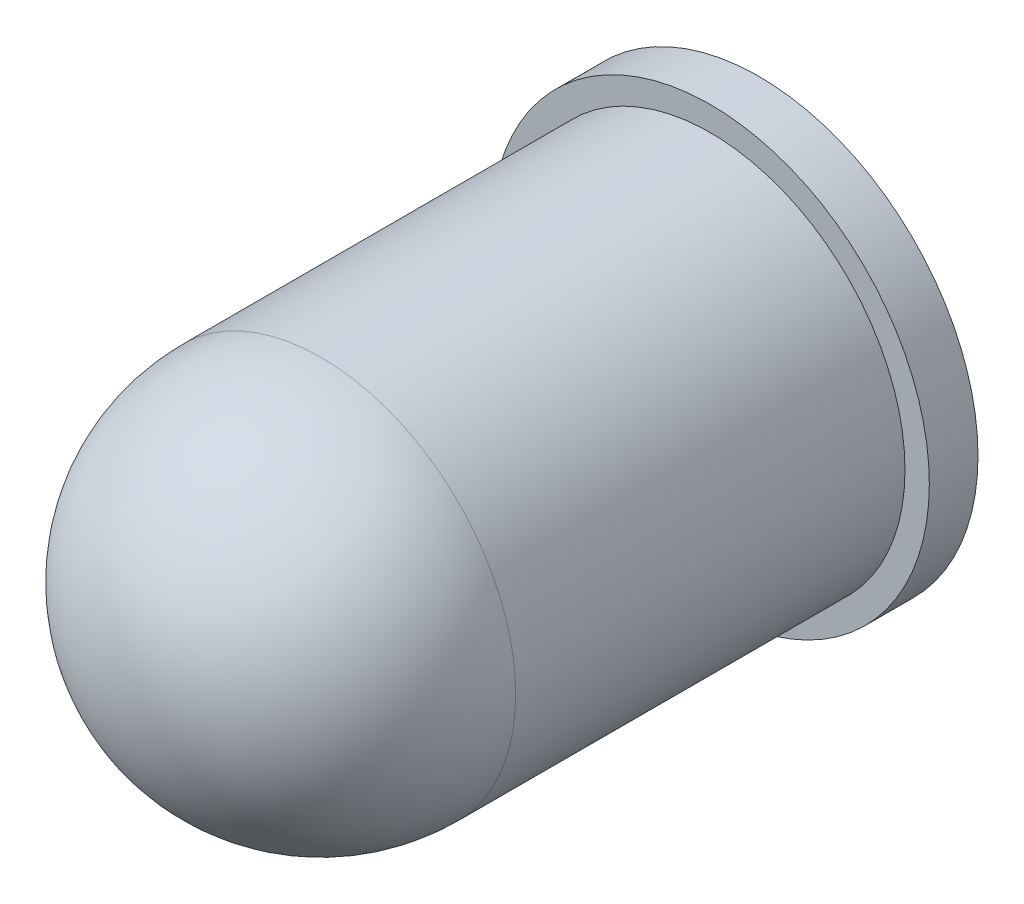
SolidWorks part; units mm, degrees
material "Glass"
ref_plane "Front Plane" through (0, 0, 0) normal (1, 0, 0) x (0, 1, 0)
ref_plane "Top Plane" through (0, 0, 0) normal (0, 0, 1) x (0, 1, 0)
ref_plane "Right Plane" through (0, 0, 0) normal (0, 1, 0) x (-1, 0, 0)
sketch "Sketch1" plane through (0, 0, 0) normal (1, 0, 0) x (0, 1, 0)
  line L0 (0, 10.8055) -> (0, -4.1754) construction
  line L1 (-3.4613, 0) -> (5.0124, 0) construction
  line L3 (0, 1) -> (4.5, 1)
  line L4 (4.5, 1) -> (4.5, 0)
  line L5 (4.5, 0) -> (0, 0)
  line L6 (4, 1) -> (4, 9)
  line L7 (4, 9) -> (0, 9)
  line L8 (0, 9) -> (0, 0)
  line L9 (0, 13) -> (0, 0)
  arc A0 (4, 9) -> (0, 13) centre (0, 9) ccw
  dimension "D4" = 12
  dimension "D1" = 1
  dimension "D2" = 9
  dimension "D3" = 8
revolve "Revolve1" add sketch "Sketch1" angle 360 about L0 region at (0, 2, 5) region at (0, 2.25, 0.5) region at (0, 1.6977, 10.6977)
shell "Shell1" thickness 1 removed face at (4.5, 0, 0)
